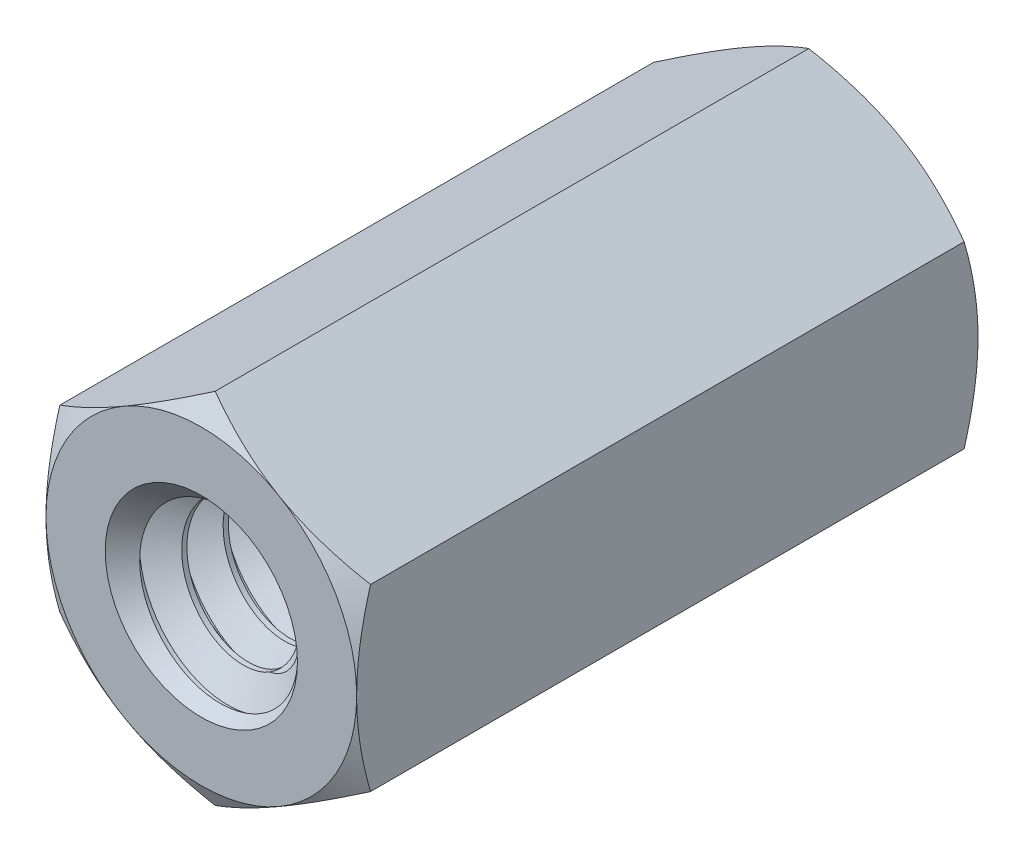
SolidWorks part; units mm, degrees
ref_plane "Front Plane" through (0, 0, 0) normal (0, 0, 1) x (1, 0, 0)
ref_plane "Top Plane" through (0, 0, 0) normal (0, 1, 0) x (1, 0, 0)
ref_plane "Right Plane" through (0, 0, 0) normal (1, 0, 0) x (0, 0, -1)
sketch "Sketch3" plane through (0, 0, 0) normal (1, 0, 0) x (0, 0, -1)
  line L0 (-4.7625, 0) -> (4.7625, 0) construction
  line L1 (0, 2.3813) -> (0, -2.3813) construction
  line L2 (-4.7625, 1.4224) -> (-4.7625, -1.4224) construction
  point P2 (-7.9375, 0)
  point P3 (7.9375, 0)
  dimension "Length" = 9.525
  dimension "Min Thread Length" = 12.7
  dimension "D1" = 12.7
  dimension "Thread Dia" = 2.8448
  dimension "Hex" = 4.7625
sketch "Sketch1" plane through (0, 0, 0) normal (0, 0, 1) x (1, 0, 0)
  line L1 (0, 2.7496) -> (-2.3813, 1.3748)
  line L2 (-2.3813, 1.3748) -> (-2.3813, -1.3748)
  line L3 (-2.3813, -1.3748) -> (0, -2.7496)
  line L4 (0, -2.7496) -> (2.3813, -1.3748)
  line L5 (2.3813, -1.3748) -> (2.3812, 1.3748)
  line L6 (2.3812, 1.3748) -> (0, 2.7496)
  circle A0 centre (0, 0) radius 2.3813 construction
  circle A1 centre (0, 0) radius 1.4224
extrude "Extrude1" add sketch "Sketch1" along normal up to vertex (4.7625 mm away) and the other way up to vertex (4.7625 mm away) up to point (0, 0, 4.7625) other way up to point (0, 0, -4.7625)
sketch "Sketch11" plane through (0, 0, -4.7625) normal (0, 0, -1) x (-1, 0, 0)
  circle A0 centre (0, 0) radius 1.4224 construction
  circle A1 centre (0, 0) radius 1.4224
curve "Helix/Spiral1" pitch 0.635 height 10.16 radius 1.4224 centre (0, 0, -4.7625) axis (0, 0, 1) start towards (0, 1, 0) parameters "Pitch"=0.635
sketch "Sketch12" plane through (0, 0, 0) normal (1, 0, 0) x (0, 0, -1)
  line L0 (5.3181, 1.4224) -> (4.7625, 1.4224)
  line L1 (5.3181, 1.4224) -> (5.08, 1.01)
  line L2 (5.08, 1.01) -> (5.0006, 1.01)
  line L3 (5.0006, 1.01) -> (4.7625, 1.4224)
  line L4 (5.0403, 1.01) -> (5.0403, 1.4224) construction
  line L5 (5.1991, 1.2162) -> (4.8816, 1.2162) construction
  dimension "D1" = 0.0794
  dimension "D2" = 0.3175
  dimension "D3" = 60
sweep "Sweep1" add profiles "Sketch12" path "Helix/Spiral1"
sketch "Sketch6" plane through (0, 0, -4.7625) normal (0, 0, -1) x (-1, 0, 0)
  line L6 (0, 2.7496) -> (-2.3812, 1.3748)
  line L7 (-2.3812, 1.3748) -> (-2.3813, -1.3748)
  line L8 (-2.3813, -1.3748) -> (0, -2.7496)
  line L9 (0, -2.7496) -> (2.3813, -1.3748)
  line L10 (2.3813, -1.3748) -> (2.3813, 1.3748)
  line L11 (2.3813, 1.3748) -> (0, 2.7496)
  line L12 (0, 2.7496) -> (-2.3812, 1.3748)
  line L13 (-2.3812, 1.3748) -> (-2.3813, -1.3748)
  line L14 (-2.3813, -1.3748) -> (0, -2.7496)
  line L15 (0, -2.7496) -> (2.3813, -1.3748)
  line L16 (2.3813, -1.3748) -> (2.3813, 1.3748)
  line L17 (2.3813, 1.3748) -> (0, 2.7496)
  dimension "D1" = 0
extrude "Extrude2" cut sketch "Sketch6" along normal through all
sketch "Sketch7" plane through (0, 0, -4.7625) normal (0, 0, -1) x (-1, 0, 0)
  circle A2 centre (0, 0) radius 1.4732
  circle A3 centre (0, 0) radius 1.4732
  dimension "D1" = 0.0508
extrude "Extrude3" cut sketch "Sketch7" against normal through all draft 43
sketch "Sketch8" plane through (0, 0, -4.7625) normal (0, 0, -1) x (-1, 0, 0)
  circle A0 centre (0, 0) radius 2.3813 construction
  circle A1 centre (0, 0) radius 2.3813
extrude "Extrude4" cut sketch "Sketch8" against normal through all draft 60 flip side to cut
mirror "Mirror1" about plane through (0, 0, 0) normal (0, 0, 1) of "Extrude2", "Extrude3", "Extrude4"
sketch "Sketch9" [suppressed] plane through (0, 0, 0) normal (1, 0, 0) x (0, 0, -1)
  line L1 (-12.7, 2.4638) -> (12.7, 2.4638)
  line L2 (-12.7, 2.4638) -> (-12.7, 0)
  line L3 (-12.7, 0) -> (12.7, 0)
  line L4 (12.7, 2.4638) -> (12.7, 0)
  line L7 (-25.4, 0) -> (25.4, 0) construction
revolve "Revolve" [suppressed] add sketch "Sketch9" angle 360 about L0
sketch "Sketch10" [suppressed] plane through (0, 0, 0) normal (1, 0, 0) x (0, 0, -1)
  line L0 (25.4, 2.413) -> (12.7, 2.413)
  line L1 (-25.4, 2.413) -> (-12.7, 2.413)
  line L2 (12.7, 2.413) -> (12.7, -2.413)
  line L3 (-25.4, -2.4638) -> (-12.7, -2.4638)
  line L4 (-12.7, 2.413) -> (-12.7, -2.4638)
  line L5 (12.7, -2.413) -> (25.4, -2.413)
equation "\"D1@Sketch3\" = \"Min Thread Length@Sketch3\""
equation "\"D3@Helix/Spiral1\" = \"Length@Sketch3\"+\"Pitch@Helix/Spiral1\""
equation "\"D1@Sketch12\" = \"Pitch@Helix/Spiral1\"*.125"
equation "\"D2@Sketch12\" = \"Pitch@Helix/Spiral1\"*.5"
